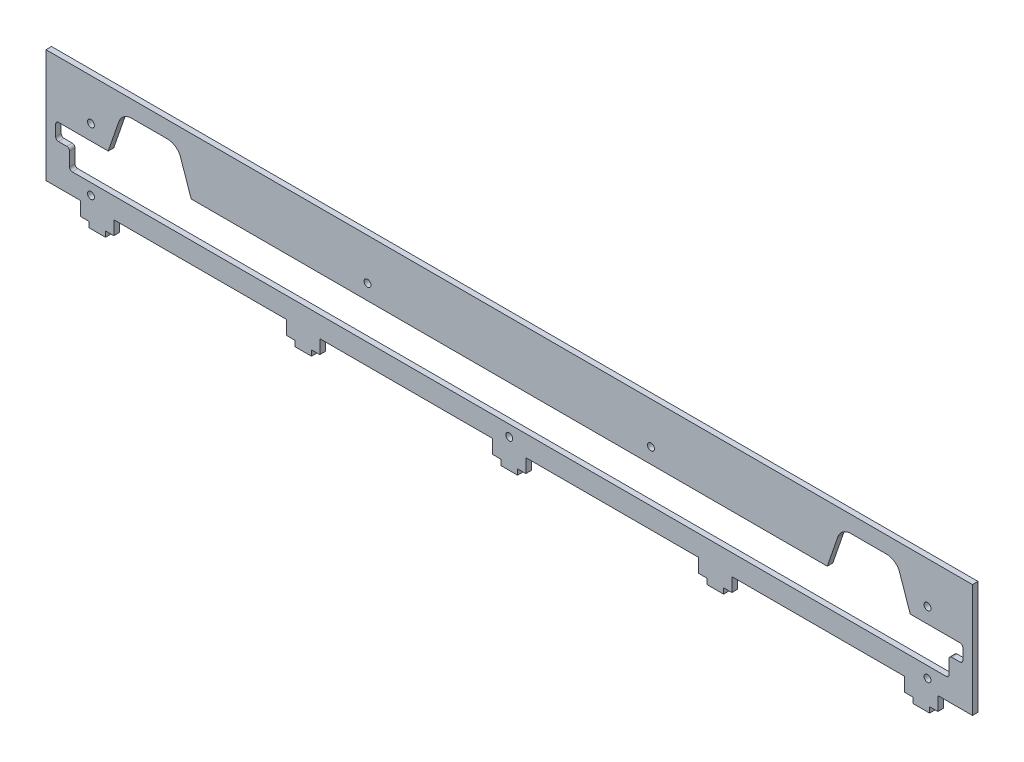
SolidWorks part; units mm, degrees
ref_plane "Спереди" through (0, 0, 0) normal (0, 0, 1) x (1, 0, 0)
ref_plane "Сверху" through (0, 0, 0) normal (0, 1, 0) x (1, 0, 0)
ref_plane "Справа" through (0, 0, 0) normal (1, 0, 0) x (0, 0, -1)
sketch "Эскиз1" plane through (0, 0, 0) normal (0, 0, 1) x (1, 0, 0)
  line L1 (-335, -46) -> (335, -46)
  line L2 (-335, -46) -> (-335, 46)
  line L3 (-335, 46) -> (335, 46)
  line L4 (335, -46) -> (335, 46)
  line L5 (0, 46) -> (0, -46) construction
  line L6 (-335, 0) -> (335, 0) construction
  point P0 (0, 0)
  dimension "D1" = 92
  dimension "D2" = 670
extrude "Бобышка-Вытянуть1" add sketch "Эскиз1" along normal mid plane 4
sketch "Эскиз2" plane through (0, 0, 2) normal (0, 0, 1) x (1, 0, 0)
  line L0 (-335, -46) -> (335, -46) construction
  line L9 (-435, -36) -> (-310, -36)
  line L10 (-435, -36) -> (-435, -46)
  line L11 (-435, -46) -> (-310, -46)
  line L12 (-310, -36) -> (-310, -46)
  line L13 (335, 46) -> (-335, 46) construction
  line L14 (-286, -36) -> (-161, -36)
  line L15 (-286, -36) -> (-286, -46)
  line L16 (-286, -46) -> (-161, -46)
  line L17 (-161, -36) -> (-161, -46)
  line L18 (-137, -36) -> (-12, -36)
  line L19 (-137, -36) -> (-137, -46)
  line L20 (-137, -46) -> (-12, -46)
  line L21 (-12, -36) -> (-12, -46)
  line L22 (12, -36) -> (137, -36)
  line L23 (12, -36) -> (12, -46)
  line L24 (12, -46) -> (137, -46)
  line L25 (137, -36) -> (137, -46)
  line L26 (161, -36) -> (286, -36)
  line L27 (161, -36) -> (161, -46)
  line L28 (161, -46) -> (286, -46)
  line L29 (286, -36) -> (286, -46)
  line L30 (310, -36) -> (435, -36)
  line L31 (310, -36) -> (310, -46)
  line L32 (310, -46) -> (435, -46)
  line L33 (435, -36) -> (435, -46)
  point P25 (-137, -41)
  point P26 (137, -41)
  dimension "D6" = 125
  dimension "D3" = 125
  dimension "D4" = 125
  dimension "D9" = 125
  dimension "D11" = 125
  dimension "D5" = 24
  dimension "D2" = 24
  dimension "D7" = 24
  dimension "D8" = 24
  dimension "D10" = 24
  dimension "D12" = 125
  dimension "D13" = 12
  dimension "D14" = 82
extrude "Вырез-Вытянуть1" cut sketch "Эскиз2" against normal through all
sketch "Эскиз3" plane through (0, 0, 2) normal (0, 0, 1) x (1, 0, 0)
  line L0 (-328, 5) -> (-328, -7)
  line L1 (-328, -7) -> (-318, -7)
  line L2 (-318, -7) -> (-318, -21)
  line L3 (-318, -21) -> (318, -21)
  line L4 (318, -21) -> (318, -7)
  line L5 (318, -7) -> (328, -7)
  line L6 (328, -7) -> (328, 5)
  line L7 (328, 5) -> (290, 5)
  line L8 (290, 5) -> (280, 34)
  line L9 (280, 34) -> (240, 34)
  line L10 (240, 34) -> (230, 5)
  line L11 (230, 5) -> (-230, 5)
  line L12 (-230, 5) -> (-240, 34)
  line L13 (-240, 34) -> (-280, 34)
  line L14 (-280, 34) -> (-290, 5)
  line L15 (-290, 5) -> (-328, 5)
  line L16 (0, 0) -> (0, 91.1092) construction
  line L17 (-260, 34) -> (-260, 12.7826) construction
  line L18 (260, 34) -> (260, 0) construction
  line L19 (-12, -36) -> (-137, -36) construction
  line L20 (-335, 46) -> (-335, -36) construction
  line L21 (335, 46) -> (-335, 46) construction
  dimension "D1" = 15
  dimension "D2" = 14
  dimension "D3" = 12
  dimension "D4" = 60
  dimension "D5" = 38
  dimension "D6" = 7
  dimension "D7" = 17
  dimension "D8" = 12
  dimension "D9" = 40
extrude "Вырез-Вытянуть2" cut sketch "Эскиз3" against normal through all
fillet "Скругление1" radius 10 4 edges at (240, 34, 0) (280, 34, 0) (-240, 34, 0) (-280, 34, 0)
fillet "Скругление6" radius 2 8 edges at (328, -7, 0) (318, -7, 0) (318, -21, 0) (-318, -21, 0) (-318, -7, 0) (-328, -7, 0) (328, 5, 0) (-328, 5, 0)
sketch "Эскиз4" plane through (0, 0, 2) normal (0, 0, 1) x (1, 0, 0)
  circle A1 centre (-302.5, -29) radius 2.5
  circle A2 centre (-302.5, -29) radius 2.5
  circle A3 centre (0, -29) radius 2.5
  circle A4 centre (0, -29) radius 2.5
  circle A5 centre (302.5, -29) radius 2.5
  circle A6 centre (302.5, -29) radius 2.5
  circle A7 centre (-102.5, 16) radius 2.5
  circle A8 centre (-102.5, 16) radius 2.5
  circle A9 centre (102.5, 16) radius 2.5
  circle A10 centre (102.5, 16) radius 2.5
  circle A11 centre (-302.5, 16) radius 2.5
  circle A12 centre (-302.5, 16) radius 2.5
  circle A13 centre (302.5, 16) radius 2.5
  circle A14 centre (302.5, 16) radius 2.5
  dimension "D1" = 0
  dimension "D2" = 0
  dimension "D3" = 0
  dimension "D4" = 0
  dimension "D5" = 0
  dimension "D6" = 0
  dimension "D7" = 0
extrude "Вырез-Вытянуть3" cut sketch "Эскиз4" against normal through all
sketch "Эскиз5" [suppressed] plane through (0, 0, 2) normal (0, 0, 1) x (1, 0, 0)
  circle A7 centre (-102.5, 16) radius 2.5
  circle A8 centre (-102.5, 16) radius 2.5
  circle A9 centre (102.5, 16) radius 2.5
  circle A10 centre (102.5, 16) radius 2.5
  circle A11 centre (-302.5, 16) radius 2.5
  circle A12 centre (-302.5, 16) radius 2.5
  circle A13 centre (302.5, 16) radius 2.5
  circle A14 centre (302.5, 16) radius 2.5
  dimension "D4" = 0
  dimension "D5" = 0
  dimension "D6" = 0
  dimension "D7" = 0
extrude "Вырез-Вытянуть4" [suppressed] cut sketch "Эскиз5" against normal through all
sketch "Эскиз6" plane through (0, -46, 0) normal (0, -1, 0) x (1, 0, 0)
  line L0 (286, -2) -> (310, -2) construction
  line L2 (310, 2) -> (286, 2) construction
  line L4 (161, 2) -> (137, 2) construction
  line L6 (137, -2) -> (161, -2) construction
  line L8 (-12, -2) -> (12, -2) construction
  line L10 (12, 2) -> (-12, 2) construction
  line L12 (-161, -2) -> (-137, -2) construction
  line L14 (-137, 2) -> (-161, 2) construction
  line L16 (-310, -2) -> (-286, -2) construction
  line L18 (-286, 2) -> (-310, 2) construction
  line L20 (292, -2) -> (304, -2)
  line L21 (304, -2) -> (304, 2)
  line L22 (304, 2) -> (292, 2)
  line L23 (292, 2) -> (292, -2)
  line L24 (155, 2) -> (143, 2)
  line L25 (143, 2) -> (143, -2)
  line L26 (143, -2) -> (155, -2)
  line L27 (155, -2) -> (155, 2)
  line L28 (-6, -2) -> (6, -2)
  line L29 (6, -2) -> (6, 2)
  line L30 (6, 2) -> (-6, 2)
  line L31 (-6, 2) -> (-6, -2)
  line L32 (-155, -2) -> (-143, -2)
  line L33 (-143, -2) -> (-143, 2)
  line L34 (-143, 2) -> (-155, 2)
  line L35 (-155, 2) -> (-155, -2)
  line L36 (-304, -2) -> (-292, -2)
  line L37 (-292, -2) -> (-292, 2)
  line L38 (-292, 2) -> (-304, 2)
  line L39 (-304, 2) -> (-304, -2)
  line L40 (298, 2) -> (298, -2) construction
  line L41 (286, 2) -> (310, 2) construction
  line L42 (149, 2) -> (149, -2) construction
  line L43 (137, 2) -> (161, 2) construction
  line L44 (0, 2) -> (0, -2) construction
  line L45 (-12, 2) -> (12, 2) construction
  line L46 (-149, 2) -> (-149, -2) construction
  line L47 (-161, 2) -> (-137, 2) construction
  line L48 (-298, 2) -> (-298, -2) construction
  line L49 (-310, 2) -> (-286, 2) construction
  point P62 (-292, 0)
  dimension "D1" = 12
  dimension "D2" = 12
  dimension "D3" = 12
  dimension "D4" = 12
  dimension "D5" = 12
extrude "Бобышка-Вытянуть2" add sketch "Эскиз6" along normal blind 4
equation "\"D3@Эскиз2\"=\"D6@Эскиз2\""
equation "\"D4@Эскиз2\"=\"D6@Эскиз2\""
equation "\"D9@Эскиз2\"=\"D6@Эскиз2\""
equation "\"D2@Эскиз2\"=\"D5@Эскиз2\""
equation "\"D7@Эскиз2\"=\"D5@Эскиз2\""
equation "\"D10@Эскиз2\"=\"D5@Эскиз2\""
equation "\"D12@Эскиз2\"=\"D6@Эскиз2\""
equation "\"D13@Эскиз2\"=\"D5@Эскиз2\"/2"
